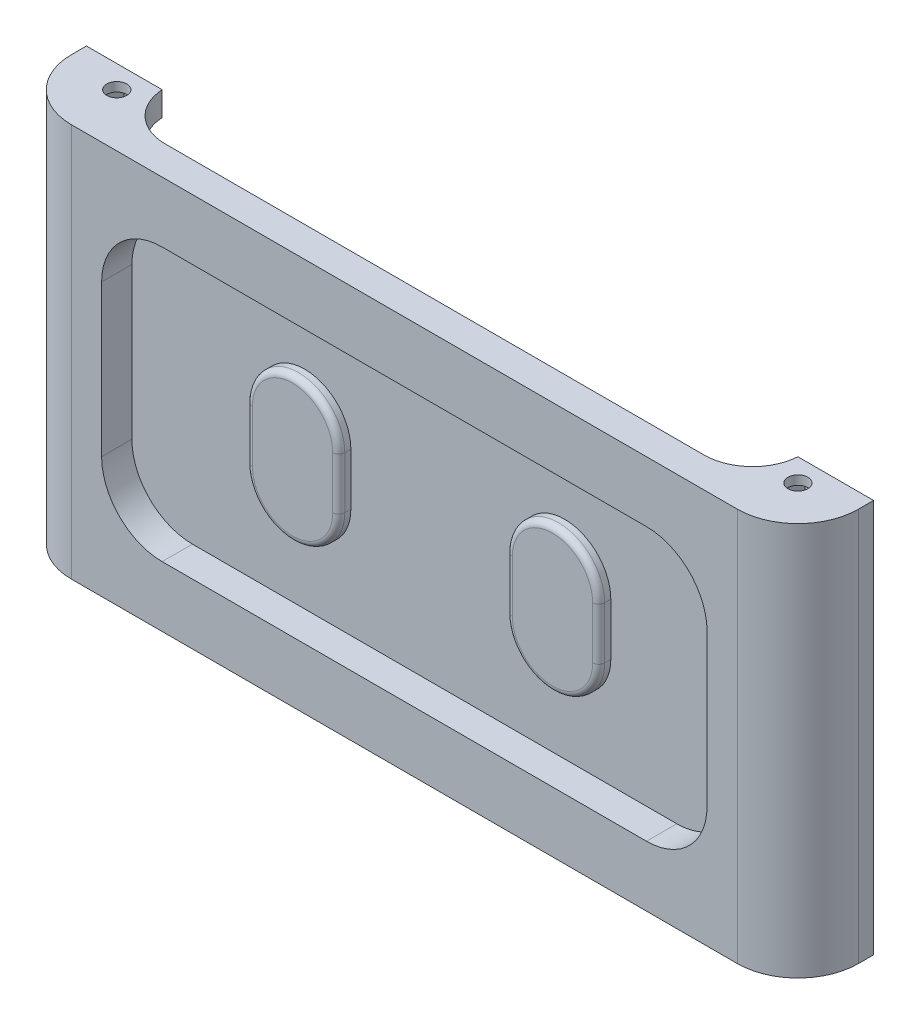
SolidWorks part; units mm, degrees
ref_plane "Front Plane" through (0, 0, 0) normal (0, 0, 1) x (1, 0, 0)
ref_plane "Top Plane" through (0, 0, 0) normal (0, 1, 0) x (1, 0, 0)
ref_plane "Right Plane" through (0, 0, 0) normal (1, 0, 0) x (0, 0, -1)
sketch "Sketch1" plane through (0, 0, 0) normal (0, 0, 1) x (1, 0, 0)
  line L1 (0, 0) -> (130, 0)
  line L2 (0, 0) -> (0, 65)
  line L3 (0, 65) -> (130, 65)
  line L4 (130, 0) -> (130, 65)
  dimension "D1" = 130
  dimension "D2" = 65
extrude "Boss-Extrude1" add sketch "Sketch1" along normal blind 12.5
sketch "Sketch4" plane through (0, 65, 0) normal (0, 1, 0) x (1, 0, 0)
  line L6 (5, 0) -> (125, 0)
  line L9 (125, 0) -> (125, -7.5)
  line L10 (5, -7.5) -> (5, 0)
  line L11 (125, -7.5) -> (5, -7.5)
  line L12 (125, 0) -> (125, -7.5)
  line L13 (5, -7.5) -> (5, 0)
  line L14 (125, -7.5) -> (5, -7.5)
  dimension "D1" = 5
extrude "Cut-Extrude3" cut sketch "Sketch4" against normal through all
sketch "Sketch2" plane through (0, 0, 12.5) normal (0, 0, 1) x (1, 0, 0)
  line L0 (65, 65) -> (65, 0) construction
  line L1 (130, 65) -> (0, 65) construction
  line L2 (0, 0) -> (130, 0) construction
  line L3 (130, 0) -> (130, 65) construction
  line L4 (15, 55) -> (115, 55)
  line L5 (15, 55) -> (15, 10)
  line L6 (15, 10) -> (115, 10)
  line L7 (115, 55) -> (115, 10)
  line L8 (15, 55) -> (115, 10) construction
  line L9 (15, 10) -> (115, 55) construction
  point P6 (65, 32.5)
  dimension "D1" = 15
  dimension "D2" = 10
extrude "Cut-Extrude1" cut sketch "Sketch2" against normal through all
fillet "Fillet1" radius 10 4 edges at (15, 10, 10) (15, 55, 10) (115, 10, 10) (115, 55, 10)
fillet "Fillet2" radius 10 2 edges at (130, 32.5, 12.5) (0, 32.5, 12.5)
sketch "Sketch5" plane through (0, 0, 0) normal (0, -1, 0) x (1, 0, 0)
  line L0 (0, 0) -> (5, 0) construction
  line L1 (5, 7.5) -> (12.5, 7.5)
  line L2 (5, 7.5) -> (5, 0)
  line L3 (5, 0) -> (12.5, 0)
  line L4 (12.5, 7.5) -> (12.5, 0)
  line L5 (125, 7.5) -> (117.5, 7.5)
  line L6 (125, 7.5) -> (125, 0)
  line L7 (125, 0) -> (117.5, 0)
  line L8 (117.5, 7.5) -> (117.5, 0)
extrude "Boss-Extrude2" add sketch "Sketch5" against normal blind 4
sketch "Sketch6" plane through (0, 4, 0) normal (0, 1, 0) x (1, 0, 0)
  line L0 (8.75, 0) -> (8.75, -7.5) construction
  line L1 (11.9254, -3.75) -> (10.3377, -1)
  line L2 (10.3377, -1) -> (7.1623, -1)
  line L3 (7.1623, -1) -> (5.5746, -3.75)
  line L4 (5.5746, -3.75) -> (7.1623, -6.5)
  line L5 (7.1623, -6.5) -> (10.3377, -6.5)
  line L6 (10.3377, -6.5) -> (11.9254, -3.75)
  line L7 (5, 0) -> (12.5, 0) construction
  line L8 (12.5, -7.5) -> (5, -7.5) construction
  line L9 (65, -12.5) -> (65, 1.5241) construction
  line L10 (120, -12.5) -> (10, -12.5) construction
  line L11 (124.4254, -3.75) -> (122.8377, -6.5)
  line L12 (122.8377, -6.5) -> (119.6623, -6.5)
  line L13 (119.6623, -6.5) -> (118.0746, -3.75)
  line L14 (118.0746, -3.75) -> (119.6623, -1)
  line L15 (119.6623, -1) -> (122.8377, -1)
  line L16 (122.8377, -1) -> (124.4254, -3.75)
  circle A0 centre (8.75, -3.75) radius 2.75 construction
  circle A1 centre (8.75, -3.75) radius 1.65
  circle A2 centre (121.25, -3.75) radius 1.65
  dimension "D1" = 3.3
  dimension "D2" = 5.5
extrude "Cut-Extrude5" cut sketch "Sketch6<2>" against normal through all contours A1 | A2 region at (8.75, 4, 3.75) region at (121.25, 4, 3.75)
sketch "Sketch6<2>" plane through (0, 4, 0) normal (0, 1, 0) x (1, 0, 0) same geometry as "Sketch6"
extrude "Cut-Extrude4" cut sketch "Sketch6" against normal blind 2.5
fillet "Fillet3" radius 8 2 edges at (117.5, 2, 7.5) (12.5, 2, 7.5)
ref_plane "Plane1" through (0, 32.5, 0) normal (0, 1, 0) x (1, 0, 0)
mirror "Mirror1" about plane through (0, 32.5, 0) normal (0, 1, 0) of "Cut-Extrude5", "Cut-Extrude4", "Boss-Extrude2", "Fillet3"
sketch "Sketch7" plane through (0, 0, 7.5) normal (0, 0, -1) x (-1, 0, 0)
  line L1 (-125, 61) -> (-5, 61)
  line L2 (-125, 61) -> (-125, 4)
  line L3 (-125, 4) -> (-5, 4)
  line L4 (-5, 61) -> (-5, 4)
extrude "Boss-Extrude3" add sketch "Sketch7" along normal blind 1 separate body
sketch "Sketch8" plane through (0, 0, 7.5) normal (0, 0, 1) x (1, 0, 0)
  line L0 (65, 55) -> (65, 24.7719) construction
  line L1 (105, 55) -> (25, 55) construction
  line L2 (25, 10) -> (105, 10) construction
  line L3 (43.5327, 36.6686) -> (86.4673, 36.6686) construction
  line L5 (65, 19.7719) -> (65, 10) construction
  line L6 (43.5327, 28.0667) -> (86.4673, 28.0667) construction
  line L7 (35.901, 36.6686) -> (35.901, 28.0667)
  line L8 (51.1643, 36.6686) -> (51.1643, 28.0667)
  line L9 (78.8357, 36.6686) -> (78.8357, 28.0667)
  line L10 (94.099, 36.6686) -> (94.099, 28.0667)
  arc A0 (51.1643, 36.6686) -> (35.901, 36.6686) centre (43.5327, 36.6686) ccw
  arc A1 (94.099, 36.6686) -> (78.8357, 36.6686) centre (86.4673, 36.6686) ccw
  arc A2 (35.901, 28.0667) -> (51.1643, 28.0667) centre (43.5327, 28.0667) ccw
  arc A3 (78.8357, 28.0667) -> (94.099, 28.0667) centre (86.4673, 28.0667) ccw
  point P11 (65, 36.6686)
extrude "Boss-Extrude4" add sketch "Sketch8" along normal blind 2 separate body contours A0 | A1 region at (43.5327, 32.3677, 7.5) region at (86.4673, 32.3677, 7.5)
sketch "Sketch9" plane through (0, 0, 6.5) normal (0, 0, -1) x (-1, 0, 0)
  line L0 (-19, 0) -> (-19, 42.7) construction
  line L1 (-20.4844, 0) -> (-109.5156, 0) construction
  line L2 (0, 0) -> (-19, 0) construction
  line L3 (-65, 65) -> (-65, 0) construction
  line L4 (-20.4844, 65) -> (-109.5156, 65) construction
  circle A0 centre (-19, 42.7) radius 8.4
  circle A1 centre (-111, 42.7) radius 8.4
  dimension "D3" = 16.8
  dimension "D1" = 19
  dimension "D2" = 42.7
extrude "Boss-Extrude6" add sketch "Sketch9" along normal blind 10 separate body
combine bodies "Combine1" operation type add bodies to combine 116 110 117
chamfer "Chamfer1" distance 3 angle 45 2 edges at (10.6, 42.7, 6.5) (102.6, 42.7, 6.5)
fillet "Fillet5" radius 1 2 edges at (10.6, 42.7, -3.5) (119.4, 42.7, -3.5)
fillet "Fillet6" radius 1 4 edges at (86.4673, 44.3003, 9.5) (94.099, 32.3677, 9.5) (86.4673, 20.4351, 9.5) (78.8357, 32.3677, 9.5)
fillet "Fillet7" radius 1 4 edges at (43.5327, 44.3003, 9.5) (51.1643, 32.3677, 9.5) (43.5327, 20.4351, 9.5) (35.901, 32.3677, 9.5)
